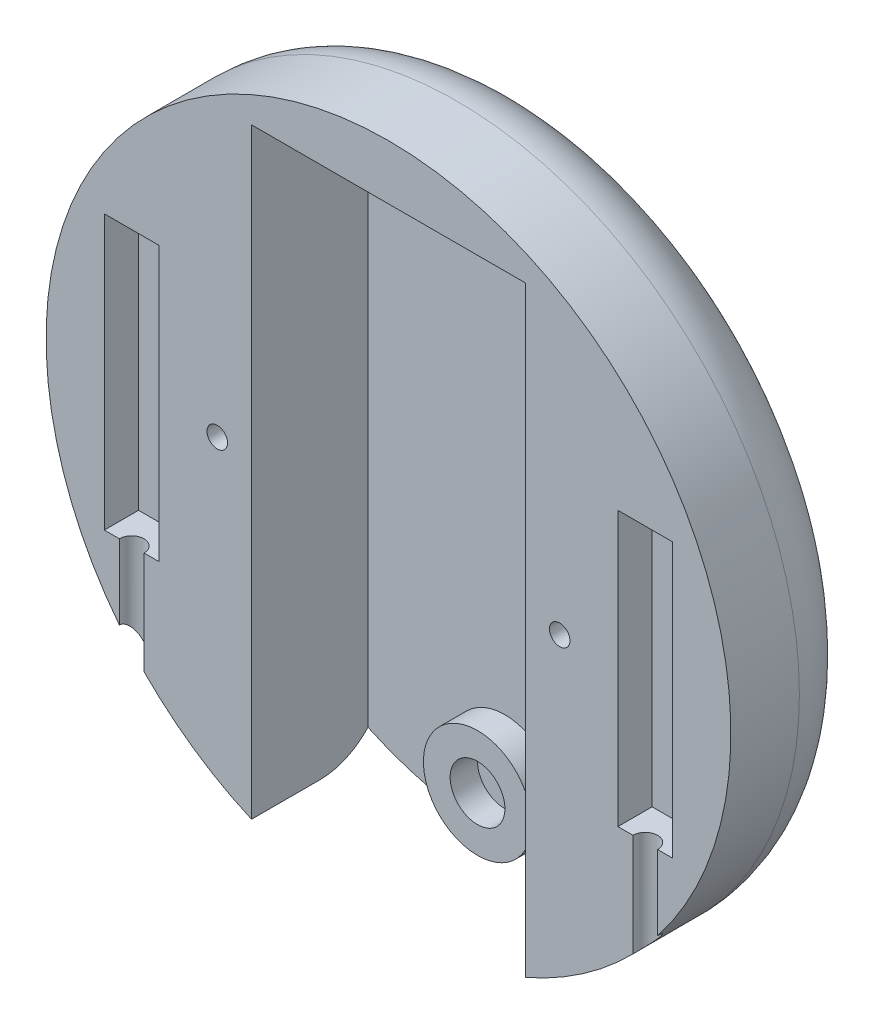
SolidWorks part; units mm, degrees
ref_plane "前视基准面" through (0, 0, 0) normal (0, 0, 1) x (1, 0, 0)
ref_plane "上视基准面" through (0, 0, 0) normal (0, 1, 0) x (1, 0, 0)
ref_plane "右视基准面" through (0, 0, 0) normal (1, 0, 0) x (0, 0, -1)
sketch "草图1" plane through (0, 0, 0) normal (0, 0, 1) x (1, 0, 0)
  circle A0 centre (0, 0) radius 50
extrude "凸台-拉伸1" add sketch "草图1" along normal blind 20
sketch "草图2" plane through (0, 0, 20) normal (0, 0, 1) x (1, 0, 0)
  line L0 (0, -50) -> (0, 50) construction
  line L1 (50, 0) -> (-50, 0) construction
  line L2 (-20, -37) -> (-20, 0)
  line L4 (-20, -37) -> (-20, -58.7545)
  line L5 (-20, -58.7545) -> (20, -58.7545)
  line L6 (-20, 0) -> (-20, 40)
  line L7 (-20, 40) -> (20, 40)
  line L8 (20, 40) -> (20, -58.7545)
  circle A0 centre (0, 0) radius 50 construction
extrude "切除-拉伸1" cut sketch "草图2" against normal blind 17
sketch "草图3" plane through (0, 0, 3) normal (0, 0, 1) x (1, 0, 0)
  circle A1 centre (0, -39) radius 7.9
  circle A3 centre (0, -39) radius 4
extrude "凸台-拉伸2" add sketch "草图3" along normal blind 4
sketch "草图4" plane through (0, 0, 20) normal (0, 0, 1) x (1, 0, 0)
  line L0 (50, 0) -> (-50, 0) construction
  line L1 (0, -50) -> (0, 50) construction
  arc A0 (20, -45.8258) -> (-20, -45.8258) centre (0, 0) ccw construction
  arc A1 (-20, -45.8258) -> (20, -45.8258) centre (0, 0) ccw construction
sketch "草图5" plane through (0, 0, 20) normal (0, 0, 1) x (1, 0, 0)
  line L0 (37.5, -24.9061) -> (37.5, 27.4879) construction
  line L3 (37.5, -20) -> (33.5, -20)
  line L4 (33.5, -20) -> (33.5, 20)
  line L5 (33.5, 20) -> (41.5, 20)
  line L6 (41.5, 20) -> (41.5, -20)
  line L7 (41.5, -20) -> (37.5, -20)
extrude "切除-拉伸2" cut sketch "草图5" against normal blind 5
sketch "草图7" plane through (0, -20, 0) normal (0, 1, 0) x (1, 0, 0)
  line L1 (50, -20) -> (-50, -20) construction
  circle A0 centre (37.5, -20) radius 1.8
extrude "切除-拉伸3" cut sketch "草图7" against normal blind 19
mirror "镜向1" about plane through (0, 0, 0) normal (1, 0, 0) of "切除-拉伸2", "切除-拉伸3"
sketch "草图8" plane through (0, 40, 0) normal (0, -1, 0) x (1, 0, 0)
  line L1 (20, 3) -> (-20, 3)
  line L2 (20, 3) -> (20, 20)
  line L3 (20, 20) -> (-20, 20)
  line L4 (-20, 3) -> (-20, 20)
extrude "切除-拉伸4" cut sketch "草图8" against normal blind 2
fillet "圆角1" radius 10 1 edges at (50, 0, 0)
sketch "草图9" plane through (0, 0, 0) normal (0, 0, -1) x (-1, 0, 0)
sketch "草图10" plane through (0, 0, 0) normal (0, 0, -1) x (-1, 0, 0)
  line L1 (-50, 0) -> (50, 0) construction
  circle A0 centre (25, 0) radius 2.5
  circle A1 centre (-25, 0) radius 2.5
extrude "切除-拉伸5" cut sketch "草图10" against normal blind 10
sketch "草图11" plane through (0, 0, 10) normal (0, 0, -1) x (-1, 0, 0)
  circle A0 centre (-25, 0) radius 1.5
  circle A1 centre (25, 0) radius 1.5
extrude "切除-拉伸6" cut sketch "草图11" against normal blind 10
